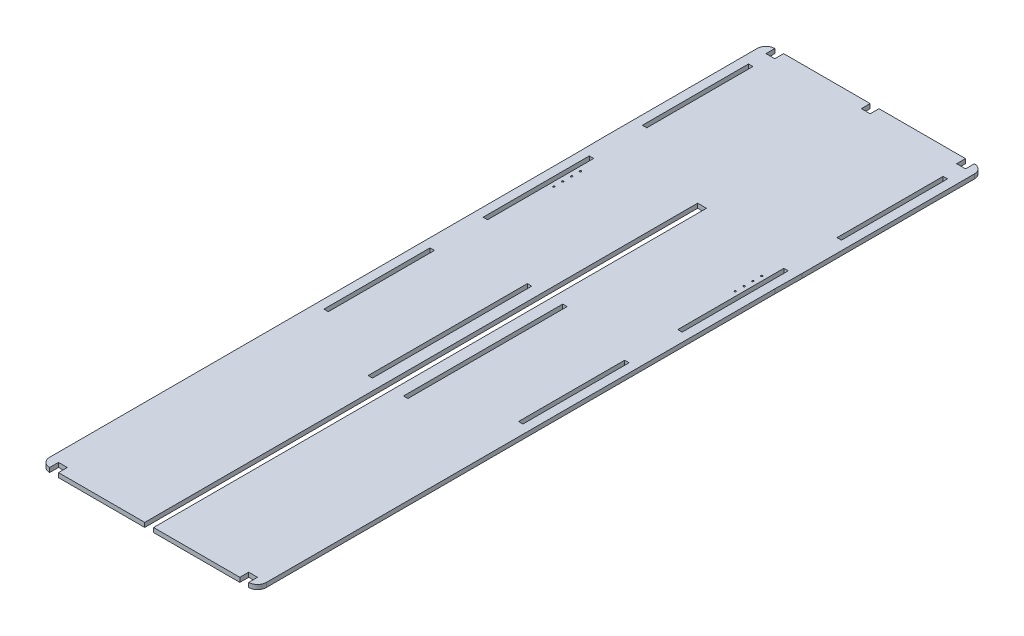
SolidWorks part; units mm, degrees
ref_plane "Front" through (0, 0, 0) normal (0, 0, 1) x (1, 0, 0)
ref_plane "Top" through (0, 0, 0) normal (0, 1, 0) x (1, 0, 0)
ref_plane "Right" through (0, 0, 0) normal (1, 0, 0) x (0, 0, -1)
sketch "Sketch2" plane through (0, 0, 0) normal (0, 1, 0) x (1, 0, 0)
  line L0 (122.5, 590) -> (122.5, -225) construction
  line L2 (0, 0) -> (0, 375)
  line L3 (0, 590) -> (245, 590)
  line L4 (245, -10) -> (245, 355)
  line L5 (10, 590) -> (10, -230) construction
  line L7 (117.5, -230) -> (117.5, 395)
  line L8 (117.5, 395) -> (127.5, 395)
  line L9 (127.5, -230) -> (127.5, 395)
  line L10 (117.5, -230) -> (127.5, 395) construction
  line L11 (117.5, 395) -> (127.5, -230) construction
  line L12 (10, -230) -> (15, -230)
  line L13 (15, -230) -> (15, 590) construction
  line L14 (235, 590) -> (235, -230) construction
  line L15 (235, -230) -> (230, -230)
  line L16 (230, -230) -> (230, 590) construction
  line L18 (0, 0) -> (0, -230)
  line L19 (245, -10) -> (245, -230)
  line L20 (0, -230) -> (117.5, -230)
  line L21 (127.5, -230) -> (245, -230)
  line L22 (-0.3, 405) -> (0, 375)
  line L23 (-0.3, 405) -> (-0.3, 590)
  line L24 (-0.3, 590) -> (0, 590)
  line L25 (10, 560) -> (15, 560)
  line L26 (245.3, 385) -> (245, 355)
  line L27 (245.3, 385) -> (245.3, 590)
  line L28 (245.3, 590) -> (245, 590)
  line L29 (10, 560) -> (10, 440)
  line L30 (10, 440) -> (15, 440)
  line L31 (15, 560) -> (15, 440)
  line L32 (15, 380) -> (10, 380)
  line L33 (15, 380) -> (15, 260)
  line L34 (15, 260) -> (10, 260)
  line L35 (10, 380) -> (10, 260)
  line L36 (10, 200) -> (15, 200)
  line L37 (10, 200) -> (10, 80)
  line L38 (10, 80) -> (15, 80)
  line L39 (15, 200) -> (15, 80)
  line L40 (230, 560) -> (235, 560)
  line L41 (230, 560) -> (230, 440)
  line L42 (230, 440) -> (235, 440)
  line L43 (235, 560) -> (235, 440)
  line L44 (230, 380) -> (235, 380)
  line L45 (230, 380) -> (230, 260)
  line L46 (230, 260) -> (235, 260)
  line L47 (235, 380) -> (235, 260)
  line L48 (230, 200) -> (235, 200)
  line L49 (230, 200) -> (230, 80)
  line L50 (230, 80) -> (235, 80)
  line L51 (235, 200) -> (235, 80)
  point P7 (122.5, 82.5)
  dimension "D1" = 245
  dimension "D2" = 820
  dimension "D3" = 195
  dimension "D4" = 10
  dimension "D5" = 590
  dimension "D6" = 10
  dimension "D7" = 5
  dimension "D8" = 10
  dimension "D9" = 5
  dimension "D10" = 30
  dimension "D11" = 120
  dimension "D12" = 60
  dimension "D13" = 0.3
  dimension "D14" = 30
  dimension "D15" = 30
  dimension "D16" = 120
  dimension "D17" = 60
  dimension "D18" = 120
  dimension "D19" = 120
  dimension "D20" = 60
  dimension "D21" = 120
  dimension "D22" = 60
  dimension "D23" = 120
extrude "Boss-Extrude1" add sketch "Sketch2" along normal blind 5 contours L4 L3 L2 L9 L7 L8 region at (8.5599, 0, -187.5)
sketch "Sketch3" plane through (0, 5, 0) normal (0, 1, 0) x (1, 0, 0)
  line L0 (20, 510.3998) -> (20, 290) construction
  line L1 (0, -230) -> (0, 375) construction
  line L2 (-0.3, 590) -> (245.3, 590) construction
  line L3 (117.5, 395) -> (127.5, 395) construction
  line L4 (105, 220) -> (100, 220)
  line L5 (105, 220) -> (105, 40)
  line L6 (105, 40) -> (100, 40)
  line L7 (100, 220) -> (100, 40)
  line L8 (117.5, -230) -> (117.5, 395) construction
  circle A0 centre (20, 330) radius 1
  circle A1 centre (20, 340) radius 1
  circle A2 centre (20, 350) radius 1
  circle A3 centre (20, 360) radius 1
  dimension "D7" = 2
  dimension "D8" = 2
  dimension "D9" = 2
  dimension "D10" = 2
  dimension "D1" = 20
  dimension "D2" = 300
  dimension "D3" = 40
  dimension "D4" = 10
  dimension "D5" = 10
  dimension "D6" = 10
  dimension "D11" = 5
  dimension "D12" = 175
  dimension "D13" = 12.5
  dimension "D14" = 180
extrude "Cut-Extrude1" cut sketch "Sketch3" against normal blind 5
ref_plane "Plane1" through (122.5, 0, 0) normal (-1, 0, 0) x (0, 0, 1)
mirror "Mirror1" about plane through (122.5, 0, 0) normal (-1, 0, 0) of "Cut-Extrude1"
fillet "Fillet1" radius 10 4 edges at (245.3, 2.5, -590) (-0.3, 2.5, -590) (0, 2.5, 230) (245, 2.5, 230)
sketch "Sketch4" plane through (0, 5, 0) normal (0, 1, 0) x (1, 0, 0)
  line L0 (235.3, 590) -> (9.7, 590) construction
  line L1 (10, -230) -> (20, -230)
  line L2 (10, -230) -> (10, -220)
  line L3 (10, -220) -> (20, -220)
  line L4 (20, -230) -> (20, -220)
  line L5 (235, -230) -> (225, -230)
  line L6 (235, -230) -> (235, -220)
  line L7 (235, -220) -> (225, -220)
  line L8 (225, -230) -> (225, -220)
  line L9 (9.7, 590) -> (19.7, 590)
  line L10 (9.7, 590) -> (9.7, 580)
  line L11 (9.7, 580) -> (19.7, 580)
  line L12 (19.7, 590) -> (19.7, 580)
  line L13 (235.3, 590) -> (225.3, 590)
  line L14 (235.3, 590) -> (235.3, 580)
  line L15 (235.3, 580) -> (225.3, 580)
  line L16 (225.3, 590) -> (225.3, 580)
  line L17 (117.5, 590) -> (127.5, 590)
  line L18 (117.5, 590) -> (117.5, 580)
  line L19 (117.5, 580) -> (127.5, 580)
  line L20 (127.5, 590) -> (127.5, 580)
  point P26 (122.5, 590)
  point P27 (122.5, 590)
  dimension "D1" = 10
  dimension "D2" = 10
  dimension "D3" = 10
  dimension "D4" = 10
  dimension "D5" = 10
  dimension "D6" = 10
  dimension "D7" = 10
  dimension "D8" = 10
  dimension "D9" = 10
  dimension "D10" = 10
extrude "Cut-Extrude2" cut sketch "Sketch4" against normal blind 10
